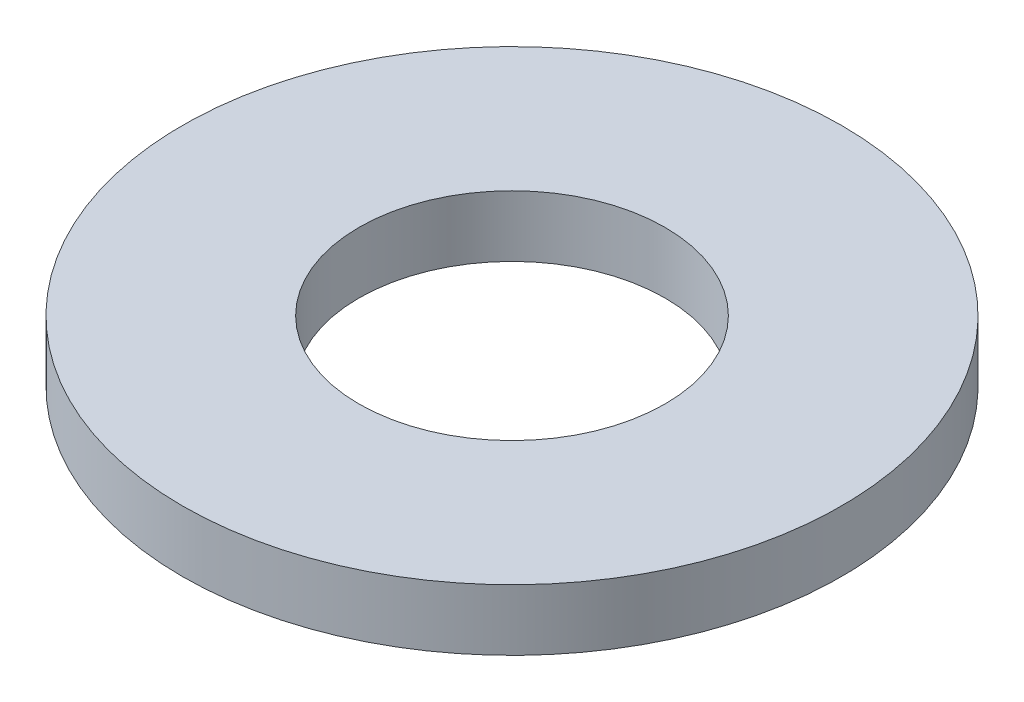
SolidWorks part; units mm, degrees
ref_plane "Front Plane" through (0, 0, 0) normal (0, 0, 1) x (1, 0, 0)
ref_plane "Top Plane" through (0, 0, 0) normal (0, 1, 0) x (1, 0, 0)
ref_plane "Right Plane" through (0, 0, 0) normal (1, 0, 0) x (0, 0, -1)
sketch "Sketch1" plane through (0, 0, 0) normal (0, 1, 0) x (1, 0, 0)
  circle A0 centre (0, 0) radius 70
  dimension "FLANGE_OD" = 140
extrude "Boss-Extrude1" add sketch "Sketch1" along normal blind 13
sketch "Sketch2" plane through (0, 0, 0) normal (0, 1, 0) x (1, 0, 0)
  circle A0 centre (0, 0) radius 32.5
  dimension "BORE_D" = 65
extrude "Cut-Extrude1" cut sketch "Sketch2" along normal through all
sketch "Sketch3" plane through (0, 13, 0) normal (0, 1, 0) x (1, 0, 0)
  circle A0 centre (0, 0) radius 28.1904 construction
  circle A1 centre (-28.1904, 0) radius 3.701
  dimension "BOLT_D" = 7.4021
  dimension "BOLT_PCD" = 56.3809
extrude "Cut-Extrude2" cut sketch "Sketch3" against normal blind 9.0913 rebuild error yes
pattern_circular "CirPattern1" count 5 over 360 rebuild error yes
